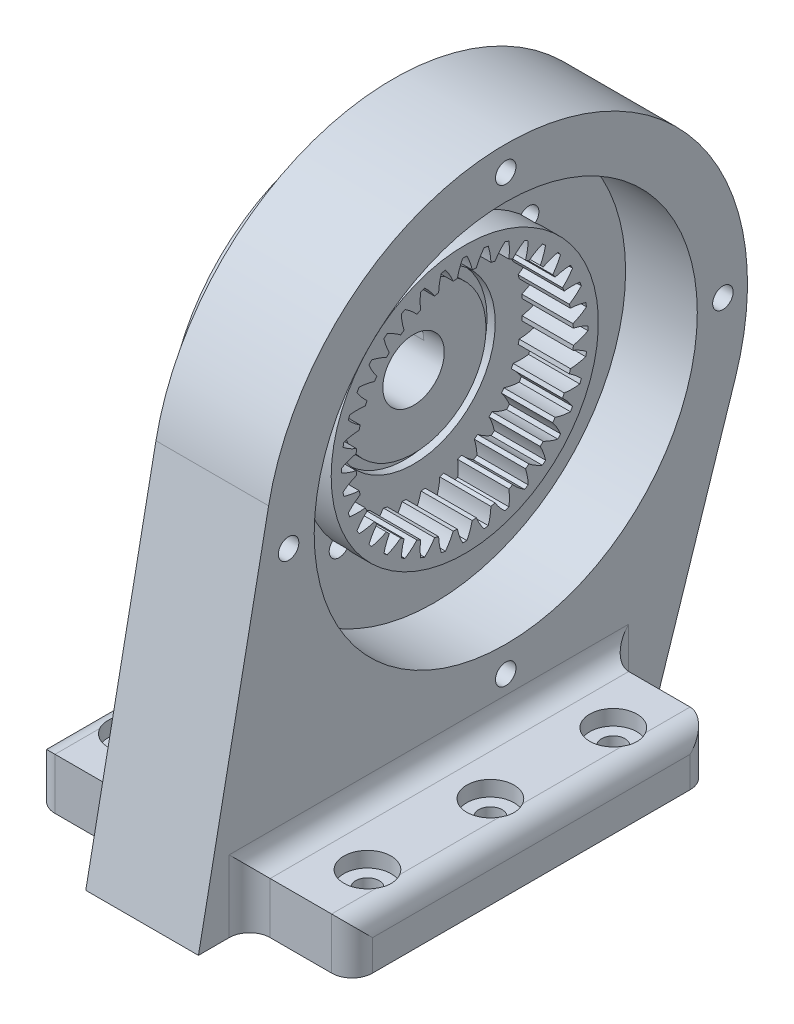
SolidWorks part; units mm, degrees
ref_plane "Plane1" through (0, 0, 0) normal (0, 0, 1) x (1, 0, 0)
ref_plane "Plane2" through (0, 0, 0) normal (0, 1, 0) x (1, 0, 0)
ref_plane "Plane3" through (0, 0, 0) normal (1, 0, 0) x (0, 0, -1)
sketch "HoldingSke" plane through (0, 0, 0) normal (0, 1, 0) x (1, 0, 0)
  line L0 (0, 0) -> (328.7845, -238.8759)
  line L1 (-15, 0) -> (100, 0) construction
  line L2 (0, 0) -> (-2.1039, 2.3779)
  line L3 (0, 0) -> (-11.863, 4.5341)
  line L4 (0, 0) -> (6.9867, 5.0761)
  line L5 (0, 0) -> (-23.7986, -8.8762)
  line L6 (0, 0) -> (-10.5278, -7.1032)
  line L7 (-2.1039, 2.3779) -> (3.3635, 27.1825)
  line L8 (-76.2, 54.61) -> (-54.61, 54.61)
  line L9 (-67.7845, 28.3722) -> (-49.3413, 33.142)
  line L10 (-76.2, 71.12) -> (104.1128, 71.12)
  line L11 (0, 0) -> (-12.7, 0)
  line L12 (-76.2, 101.6) -> (-76.1428, 101.6)
  line L13 (24.9733, 27.94) -> (52.9518, 28.4284)
  line L14 (24.9733, 27.94) -> (24.9746, 27.94)
  line L15 (24.9733, 27.94) -> (100.4006, 29.5858)
  circle A0 centre (0, 0) radius 12.7
  circle A1 centre (0, 0) radius 12.7
  circle A2 centre (0, 0) radius 12.7
  dimension "MHD" = 25.4
  dimension "Hub_dia" = 25.4
  dimension "Diameter" = 25.4
  dimension "Num_teeth" = 36
  dimension "Pitch" = 406.4
  dimension "Overall_len" = 25.4
  dimension "Show_teeth" = 36
  dimension "Thickness" = 12.7
  dimension "OAL" = 25.4001
  dimension "T_dim" = 21.59
  dimension "Ap" = 14.5
  dimension "H" = 19.05
  dimension "Pitch_radius" = 180.3128
  dimension "Width" = 12.7
  dimension "Backlash" = 0.0571
  dimension "Addendum_fac" = 1
  dimension "Dedendum_fac" = 1.25
  dimension "Clearance_fac" = 0.25
  dimension "Dedendum_add" = 0.0013
sketch "BasProSke" plane through (0, 0, 0) normal (0, 1, 0) x (1, 0, 0)
  line L0 (-10, 0) -> (60, 0) construction
  line L1 (0, 26.9875) -> (0, 30.586)
  line L2 (0, 26.9875) -> (12.7, 26.9875)
  line L3 (12.7, 26.9875) -> (12.7, 30.586)
  line L4 (12.7, 30.586) -> (0, 30.586)
  dimension "Thickness" = 12.7
  dimension "Diameter" = 61.1721
  dimension "Inside_diameter" = 53.975
revolve "Base-Revolve" add sketch "BasProSke" angle 360 about L0
sketch "TooCutSke" plane through (0, 0, 0) normal (1, 0, 0) x (0, 0, -1)
  line L3 (1.3893, 28.5412) -> (1.3893, 53.6633) construction
  line L4 (0, 0) -> (0, 59.563) construction
  line L5 (0, 0) -> (-5.9551, 68.0675) construction
  line L6 (-12.1342, 23.9318) -> (35.5288, 28.1018) construction
  circle A0 centre (0, 0) radius 28.575 construction
  circle A1 centre (0, 0) radius 30.5606 construction
  circle A2 centre (0, 0) radius 24.8983 construction
  circle A3 centre (0, 0) radius 26.9621 construction
  arc A4 (1.8417, 26.8991) -> (0.5248, 30.5561) centre (-12.1342, 23.9318) ccw
  arc A5 (1.8417, 26.8991) -> (-1.8417, 26.8991) centre (0, 0) ccw
  arc A6 (0.5248, 30.5561) -> (-0.5248, 30.5561) centre (0, 0) ccw
  arc A7 (-0.5248, 30.5561) -> (-1.8417, 26.8991) centre (12.1342, 23.9318) ccw
  dimension "Pitch_dia" = 57.15
  dimension "Base_dia" = 49.7967
  dimension "Root_dia" = 61.1213
  dimension "Overcut_dia" = 53.9242
  dimension "Flank_rad" = 14.2875
  dimension "Half_ang" = 5
  dimension "Half_CT" = 1.3893
extrude "ToothCut" cut sketch "TooCutSke" along normal through all
fillet "Breaks" [suppressed] radius 0.1588
fillet "RootFillets" [suppressed] radius 0.3981
pattern_circular "TeethCuts" count 36 over 360 about axis through (0, 0, 0) along (1, 0, 0) of "RootFillets", "Breaks", "ToothCut"
sketch "Sketch3" plane through (0, 0, 0) normal (1, 0, 0) x (0, 0, -1)
  circle A0 centre (0, 0) radius 30.586 construction
  circle A1 centre (0, 0) radius 30.586
extrude "Extrude-Thin1" add sketch "Sketch3" along normal up to surface (12.7 mm away) thin
sketch "Sketch4" plane through (0, 0, 0) normal (1, 0, 0) x (0, 0, -1)
  circle A0 centre (0, 0) radius 33.126 construction
  circle A1 centre (0, 0) radius 33.126
extrude "Extrude-Thin2" add sketch "Sketch4" along normal blind 5.08 thin
sketch "Sketch5" plane through (0, 0, 0) normal (1, 0, 0) x (0, 0, -1)
  circle A0 centre (0, 0) radius 28.575 construction
  dimension "D1" = 57.15
sketch "Sketch9" plane through (0, 0, 0) normal (-1, 0, 0) x (0, 0, 1)
  circle A0 centre (0, 0) radius 59.944
  circle A1 centre (0, 0) radius 39.476 construction
  circle A2 centre (0, 0) radius 39.476
  dimension "D1" = 119.888
extrude "Boss-Extrude2" add sketch "Sketch9" against normal up to surface (5.08 mm away) up to face at (5.08, 0, -39.476)
sketch "Sketch12" plane through (0, 0, 0) normal (-1, 0, 0) x (0, 0, 1)
  circle A23 centre (0, 0) radius 59.944
  circle A43 centre (0, 0) radius 59.944
  dimension "D1" = 0
extrude "Boss-Extrude3" add sketch "Sketch12" along normal blind 5.08 contours A43
sketch "Sketch13" plane through (0, 0, 0) normal (1, 0, 0) x (0, 0, -1)
  circle A0 centre (0, 0) radius 20.2565
  circle A1 centre (0, 0) radius 17.9705
  dimension "D1" = 40.513
  dimension "D2" = 35.941
extrude "Cut-Extrude10" cut sketch "Sketch13" against normal blind 2.032
sketch "Sketch14" plane through (-5.08, 0, 0) normal (-1, 0, 0) x (0, 0, 1)
  circle A0 centre (0, 0) radius 3.302
  dimension "D1" = 6.604
extrude "Cut-Extrude11" cut sketch "Sketch14" against normal through all both and the other way through all
sketch "Sketch15" plane through (5.08, 0, 0) normal (1, 0, 0) x (0, 0, -1)
  circle A0 centre (0, 0) radius 47.498
  circle A1 centre (0, 0) radius 59.944 construction
  circle A2 centre (0, 0) radius 59.944
  dimension "D1" = 12.446
extrude "Boss-Extrude5" add sketch "Sketch15" along normal blind 17.78
sketch "Sketch16" plane through (22.86, 0, 0) normal (1, 0, 0) x (0, 0, -1)
  line L0 (0, 56.388) -> (0, 59.944) construction
  line L1 (0, 51.308) -> (0, 47.498) construction
  line L2 (56.388, 0) -> (59.944, 0) construction
  line L3 (51.308, 0) -> (47.498, 0) construction
  line L4 (0, -56.388) -> (0, -59.944) construction
  line L5 (0, -51.308) -> (0, -47.498) construction
  line L6 (-56.388, 0) -> (-59.944, 0) construction
  line L7 (-51.308, 0) -> (-47.498, 0) construction
  line L8 (0, 0) -> (-47.498, 0) construction
  circle A2 centre (0, 0) radius 59.944 construction
  circle A3 centre (0, 53.848) radius 2.54 construction
  circle A4 centre (0, 0) radius 47.498 construction
  circle A5 centre (53.848, 0) radius 2.54 construction
  circle A6 centre (0, -53.848) radius 2.54 construction
  circle A7 centre (-53.848, 0) radius 2.54 construction
  point P4 (0, 56.388)
  point P19 (56.388, 0)
  point P26 (0, -56.388)
  point P33 (-56.388, 0)
  point P38 (0, 0)
  dimension "D2" = 5.08
  dimension "D1" = 3.556
  dimension "D3" = 4
hole_wizard "CBORE for #00 Binding Head Machine Screw1" positions "Sketch18" profile "Sketch19" counterbore size "#00" standard "ANSI Inch" end condition through all
sketch "Sketch18" plane through (-5.08, 0, 0) normal (-1, 0, 0) x (0, 0, 1)
  point P0 (0, 53.848)
  point P3 (53.848, 0)
  point P6 (0, -53.848)
  point P9 (-53.848, 0)
sketch "Sketch19" plane through (-5.08, 53.848, 0) normal (0, 1, 0) x (0, 0, 1)
  line L0 (0, 0) -> (0, 27.94)
  line L1 (0, 27.94) -> (2.54, 27.94)
  line L3 (2.54, 27.94) -> (2.54, 1.27)
  line L4 (2.54, 1.27) -> (3.81, 1.27)
  line L5 (3.81, 1.27) -> (3.81, 0)
  line L7 (3.81, 0) -> (0, 0)
  line L11 (0, -6.35) -> (0, 107.95) construction
  dimension "Thru Hole Dia." = 5.08
  dimension "Thru Hole Depth" = 27.94
  dimension "C'Bore Dia." = 7.62
  dimension "C'Bore Depth" = 1.27
sketch "Sketch21" plane through (-5.08, 0, 0) normal (-1, 0, 0) x (0, 0, 1)
  circle A0 centre (0, 0) radius 19.05
  dimension "D1" = 38.1
extrude "Cut-Extrude12" cut sketch "Sketch21" against normal blind 1.524
sketch "Sketch22" plane through (-5.08, 0, 0) normal (-1, 0, 0) x (0, 0, 1)
  circle A0 centre (23.5, -23.5) radius 2.5
  circle A1 centre (-23.5, -23.5) radius 2.5
  circle A2 centre (-23.5, 23.5) radius 2.5
  circle A3 centre (23.5, 23.5) radius 2.5
  circle A4 centre (0, 0) radius 3.302 construction
  dimension "D1" = 5
  dimension "D4" = 23.5
  dimension "D5" = 23.5
  dimension "D2" = 47
  dimension "D3" = 47
extrude "Cut-Extrude13" cut sketch "Sketch22" against normal through all
sketch "Sketch23" plane through (12.7, 0, 0) normal (1, 0, 0) x (0, 0, -1)
  circle A0 centre (23.5, 23.5) radius 2.794
  circle A1 centre (-23.5, 23.5) radius 2.794
  circle A2 centre (-23.5, -23.5) radius 2.794
  circle A3 centre (23.5, -23.5) radius 2.794
  dimension "D1" = 5.588
extrude "Cut-Extrude14" cut sketch "Sketch23" against normal up to surface (7.62 mm away) up to face at (5.08, 0, 0)
sketch "Sketch24" plane through (12.7, 0, 0) normal (1, 0, 0) x (0, 0, -1)
  arc A2 (25.31, 21.3715) -> (21.3715, 25.31) centre (0, 0) ccw
  arc A4 (21.3715, 25.31) -> (-21.3715, 25.31) centre (0, 0) ccw construction
  arc A5 (25.31, -21.3715) -> (21.3715, -25.31) centre (23.5, -23.5) ccw construction
  arc A6 (-21.3715, -25.31) -> (-25.31, -21.3715) centre (-23.5, -23.5) ccw construction
  arc A7 (-25.31, 21.3715) -> (-21.3715, 25.31) centre (-23.5, 23.5) ccw construction
  arc A8 (21.3715, 25.31) -> (25.31, 21.3715) centre (23.5, 23.5) ccw construction
  arc A9 (25.31, -21.3715) -> (21.3715, -25.31) centre (23.5, -23.5) ccw
  arc A10 (-21.3715, -25.31) -> (-25.31, -21.3715) centre (-23.5, -23.5) ccw
  arc A11 (-25.31, 21.3715) -> (-21.3715, 25.31) centre (-23.5, 23.5) ccw
  arc A12 (21.3715, 25.31) -> (25.31, 21.3715) centre (23.5, 23.5) ccw
  arc A14 (21.3715, -25.31) -> (25.31, -21.3715) centre (0, 0) ccw
  arc A15 (-25.31, -21.3715) -> (-21.3715, -25.31) centre (0, 0) ccw
  arc A16 (-21.3715, 25.31) -> (-25.31, 21.3715) centre (0, 0) ccw
extrude "Boss-Extrude6" add sketch "Sketch24" against normal blind 3.81
sketch "Sketch26" plane through (-3.556, 0, 0) normal (-1, 0, 0) x (0, 0, 1)
  circle A0 centre (0, 0) radius 7.62
  dimension "D1" = 15.24
extrude "Cut-Extrude15" cut sketch "Sketch26" against normal through all
sketch "Sketch27" plane through (-5.08, 0, 0) normal (-1, 0, 0) x (0, 0, 1)
  circle A0 centre (0, 0) radius 44.45
  dimension "D1" = 88.9
sketch "Sketch28" plane through (-3.556, 0, 0) normal (-1, 0, 0) x (0, 0, 1)
  circle A1 centre (0, 0) radius 19.05
  circle A2 centre (0, 0) radius 19.05
  circle M2 centre (0, 0) radius 7.62
  circle M3 centre (0, 0) radius 19.05
  dimension "D1" = 0
extrude "Boss-Extrude8" add sketch "Sketch28" along normal up to surface (1.524 mm away) contours M3 M2 up to face at (-5.08, 23.5, 26)
sketch "Sketch29" plane through (-5.08, 0, 0) normal (-1, 0, 0) x (0, 0, 1)
  circle A0 centre (0, 0) radius 44.45
  dimension "D1" = 88.9
extrude "Boss-Extrude9" add sketch "Sketch29" along normal blind 11.62
sketch "Sketch30" plane through (-5.08, 0, 0) normal (1, 0, 0) x (0, 0, -1)
  circle A0 centre (23.5, -23.5) radius 2.5 construction
  circle A1 centre (0, 0) radius 7.62
  circle A2 centre (0, 0) radius 7.62
  circle A3 centre (23.5, 23.5) radius 2.5 construction
  circle A4 centre (-23.5, 23.5) radius 2.5 construction
  circle A5 centre (-23.5, -23.5) radius 2.5 construction
  circle A6 centre (23.5, -23.5) radius 2.5
  circle A7 centre (23.5, 23.5) radius 2.5
  circle A8 centre (-23.5, 23.5) radius 2.5
  circle A9 centre (-23.5, -23.5) radius 2.5
  dimension "D1" = 0
extrude "Cut-Extrude16" cut sketch "Sketch30" against normal through all
sketch "Sketch31" plane through (-16.7, 0, 0) normal (-1, 0, 0) x (0, 0, 1)
  line L0 (0, 0) -> (0, 59.944) construction
  line L2 (-7.62, 0) -> (7.62, 0)
  line L3 (-7.62, 0) -> (-7.62, 50.8)
  line L4 (-7.62, 50.8) -> (7.62, 50.8)
  line L5 (7.62, 0) -> (7.62, 50.8)
  line L6 (-7.62, 0) -> (7.62, 50.8) construction
  line L7 (-7.62, 50.8) -> (7.62, 0) construction
  circle A0 centre (0, 0) radius 59.944 construction
  circle A1 centre (0, 0) radius 7.62 construction
  point P6 (0, 25.4)
  dimension "D1" = 50.8
  dimension "D2" = 0
extrude "Cut-Extrude17" cut sketch "Sketch31" against normal up to surface (11.62 mm away) up to face at (-5.08, 0, 44.45)
sketch "Sketch32" plane through (-16.7, 0, 0) normal (-1, 0, 0) x (0, 0, 1)
  circle A0 centre (0, 0) radius 19.05
  dimension "D1" = 38.1
extrude "Cut-Extrude18" cut sketch "Sketch32" against normal blind 1.6
sketch "Sketch33" plane through (5.08, 0, 0) normal (1, 0, 0) x (0, 0, -1)
  circle A0 centre (-23.5, 23.5) radius 3.048
  dimension "D1" = 6.096
extrude "Cut-Extrude19" cut sketch "Sketch33" along normal up to surface (3.81 mm away) up to face at (8.89, 22.474, 22.474)
pattern_circular "CirPattern1" count 4 over 360 about axis through (0, 0, 0) along (1, 0, 0) of "Cut-Extrude19"
sketch "Sketch34" plane through (22.86, 0, 0) normal (1, 0, 0) x (0, 0, -1)
  line L0 (-76.2, -76.2) -> (38.1, -76.2)
  line L1 (-58.8018, 11.6459) -> (-76.2, -76.2)
  line L2 (56.9605, -18.6757) -> (38.1, -76.2)
  circle A1 centre (0, 0) radius 59.944 construction
  circle A2 centre (0, 0) radius 59.944
  circle M9 centre (0, 0) radius 59.944
  dimension "D1" = 114.3
  dimension "D2" = 76.2
  dimension "D3" = 76.2
extrude "Boss-Extrude10" add sketch "Sketch34" against normal up to surface (27.94 mm away) contours L2 L1 L0 M9 up to face at (-5.08, 1.7405, 0)
sketch "Sketch35" plane through (0, -76.2, 0) normal (0, -1, 0) x (1, 0, 0)
  line L0 (-5.08, -38.1) -> (22.86, -38.1) construction
  line L1 (8.89, 76.2) -> (8.89, -38.1) construction
  line L2 (48.26, 82.4565) -> (48.26, -31.8435)
  line L3 (-5.08, 76.2) -> (22.86, 76.2) construction
  line L4 (22.86, 76.2) -> (22.86, -38.1) construction
  line L5 (-30.48, 82.4565) -> (-30.48, -31.8435)
  arc A0 (-30.48, -31.8435) -> (48.26, -31.8435) centre (8.89, 88.9) ccw
  arc A1 (-30.48, 82.4565) -> (48.26, 82.4565) centre (8.89, 203.2) ccw
  dimension "D1" = 254
  dimension "D2" = 254
  dimension "D3" = 25.4
ref_plane "Plane4" through (8.89, 0, 0) normal (-1, 0, 0) x (0, 0, 1)
sketch "Sketch44" plane through (22.86, 0, 0) normal (1, 0, 0) x (0, 0, -1)
  line L1 (-61.8279, -59.9939) -> (-46.968, -59.9939)
  line L2 (-61.8279, -59.9939) -> (-61.8279, -65.5544)
  line L3 (-61.8279, -65.5544) -> (-46.968, -65.5544)
  line L4 (-46.968, -59.9939) -> (-46.968, -65.5544)
sketch "Sketch45" plane through (22.86, 0, 0) normal (1, 0, 0) x (0, 0, -1)
  line L0 (-76.2, -76.2) -> (38.1, -76.2) construction
  line L1 (-63.5, -76.2) -> (25.4, -76.2)
  line L2 (-63.5, -76.2) -> (-63.5, -63.5)
  line L3 (-63.5, -63.5) -> (25.4, -63.5)
  line L4 (25.4, -76.2) -> (25.4, -63.5)
  line L5 (-19.05, -76.2) -> (-19.05, -63.5) construction
  point P8 (-19.05, -63.5)
  dimension "D1" = 88.9
  dimension "D2" = 12.7
extrude "Boss-Extrude12" add sketch "Sketch45" along normal blind 25.4 and the other way offset from surface (53.34 mm away) 25.4
fillet "Fillet2" radius 5.08 6 edges at (-5.08, -69.85, 63.5) (22.86, -69.85, 63.5) (-5.08, -69.85, -25.4) (22.86, -69.85, -25.4) (-5.08, -63.5, 19.05) (22.86, -63.5, 19.05)
fillet "Fillet3" radius 5.08 6 edges at (-30.48, -69.85, -25.4) (-30.48, -63.5, 19.05) (-30.48, -69.85, 63.5) (48.26, -69.85, -25.4) (48.26, -69.85, 63.5) (48.26, -63.5, 19.05)
hole_wizard "CBORE for M5 Hex Head Machine Screw1" positions "Sketch46" profile "Sketch47" counterbore size "M5" standard "ANSI Metric"
sketch "Sketch46" plane through (0, -63.5, 0) normal (0, 1, 0) x (1, 0, 0)
  line L5 (-20.32, -63.5) -> (-20.32, 25.4) construction
  line L6 (-25.4, 25.4) -> (-10.16, 25.4) construction
  line L8 (-30.48, -58.42) -> (-30.48, 20.32) construction
  line L9 (-25.4, -63.5) -> (-10.16, -63.5) construction
  line L10 (38.1, 25.4) -> (38.1, -63.5) construction
  line L11 (27.94, 25.4) -> (43.18, 25.4) construction
  line L12 (27.94, -63.5) -> (43.18, -63.5) construction
  line L14 (48.26, 20.32) -> (48.26, -58.42) construction
  line L15 (-20.32, 11.43) -> (38.1, 11.43) construction
  line L17 (-20.32, -49.53) -> (38.1, -49.53) construction
  point P22 (-20.32, -19.05)
  point P24 (-20.32, 11.43)
  point P26 (-20.32, -49.53)
  point P39 (38.1, 11.43)
  point P43 (38.1, -49.53)
  point P46 (38.1, -19.05)
  dimension "D1" = 10.16
  dimension "D2" = 30.48
  dimension "D3" = 30.48
  dimension "D4" = 10.16
sketch "Sketch47" plane through (38.1, -63.5, 19.05) normal (1, 0, 0) x (0, 0, 1)
  line L0 (0, 0) -> (0, 12.7)
  line L1 (0, 12.7) -> (2.9, 12.7)
  line L3 (2.9, 12.7) -> (2.9, 3.8)
  line L4 (2.9, 3.8) -> (5.855, 3.8)
  line L5 (5.855, 3.8) -> (5.855, 0)
  line L7 (5.855, 0) -> (0, 0)
  line L11 (0, -6.35) -> (0, 107.95) construction
  dimension "Thru Hole Dia." = 5.8
  dimension "Thru Hole Depth" = 12.7
  dimension "C'Bore Dia." = 11.71
  dimension "C'Bore Depth" = 3.8
equation "' \"Pitch@HoldingSke\" = 4"
equation "' \"Num_teeth@HoldingSke\" = 24"
equation "' \"Ap@HoldingSke\" =  14.5"
equation "' \"Ap@HoldingSke\" = 14.5"
equation "' \"Width@HoldingSke\" = 0.5"
equation "' \"Diameter@HoldingSke\" = 8"
equation "' \"Show_teeth@HoldingSke\" = 100"
equation "' \"Backlash@HoldingSke\" = 0.009"
equation "' \"Addendum_fac@HoldingSke\" = 1.0"
equation "' \"Dedendum_fac@HoldingSke\" = 1.25"
equation "' \"Dedendum_add@HoldingSke\" = 0.00005"
equation "' \"Clearance_fac@HoldingSke\" = 0.25"
equation "\"Overcut_dia@TooCutSke\" = (\"Num_teeth@HoldingSke\" - 2 * \"Addendum_fac@HoldingSke\") / \"Pitch@HoldingSke\" - 0.002"
equation "\"Pitch_dia@TooCutSke\" = \"Num_teeth@HoldingSke\" / \"Pitch@HoldingSke\""
equation "\"Base_dia@TooCutSke\" = \"Num_teeth@HoldingSke\" / \"Pitch@HoldingSke\" * cos((\"Ap@HoldingSke\"  * 3.14159265 / 180)) * 0.90"
equation "\"Root_dia@TooCutSke\" = \"Num_teeth@HoldingSke\"  / \"Pitch@HoldingSke\" + 2 *  \"Dedendum_fac@HoldingSke\"/ \"Pitch@HoldingSke\" + \"Dedendum_add@HoldingSke\" * 2"
equation "\"Half_ang@TooCutSke\" = 180 / \"Num_teeth@HoldingSke\""
equation "\"Half_CT@TooCutSke\" = \"Num_teeth@HoldingSke\" / \"Pitch@HoldingSke\" * sin((3.14159265 / 2 / \"Num_teeth@HoldingSke\")) / 2 + 10 * \"Backlash@HoldingSke\" / 4"
equation "\"Flank_rad@TooCutSke\" = \"Num_teeth@HoldingSke\" / \"Pitch@HoldingSke\" / 4"
equation "\"Radius@RootFillets\"= \"Clearance_fac@HoldingSke\" / \"Pitch@HoldingSke\" + \"Dedendum_add@HoldingSke\""
equation "\"Break_rad@Breaks\" = 0.02 / \"Pitch@HoldingSke\" * 5"
equation "\"Num_teeth@TeethCuts\" = int( \"Show_teeth@HoldingSke\" ) + 1"
equation "\"Num_teeth@TeethCuts\" = ((sgn( \"Num_teeth@TeethCuts\" - \"Num_teeth@HoldingSke\" )-1)*( \"Num_teeth@TeethCuts\" - \"Num_teeth@HoldingSke\" ))/-2+ \"Num_teeth@HoldingSke\""
equation "\"Num_teeth@TeethCuts\" = ((sgn( \"Num_teeth@TeethCuts\" - 2.0)+1)*( \"Num_teeth@TeethCuts\" - 2.0))/2 +2.0"
equation "\"Angle@TeethCuts\" = 360.0 / \"Num_teeth@HoldingSke\""
equation "\"Diameter@BasProSke\" = \"Num_teeth@HoldingSke\"  / \"Pitch@HoldingSke\" + 2 *  \"Dedendum_fac@HoldingSke\"/ \"Pitch@HoldingSke\" + \"Dedendum_add@HoldingSke\" * 2 + 0.002"
equation "\"Diameter@BasProSke\" = ((sgn( \"Diameter@BasProSke\"  - \"Diameter@HoldingSke\" )+1)*( \"Diameter@BasProSke\"  - \"Diameter@HoldingSke\" ))/2 + \"Diameter@HoldingSke\""
equation "\"Inside_diameter@BasProSke\" =  (\"Num_teeth@HoldingSke\" - 2 * \"Addendum_fac@HoldingSke\") / \"Pitch@HoldingSke\" "
equation "\"Thickness@BasProSke\"  = \"Width@HoldingSke\""
